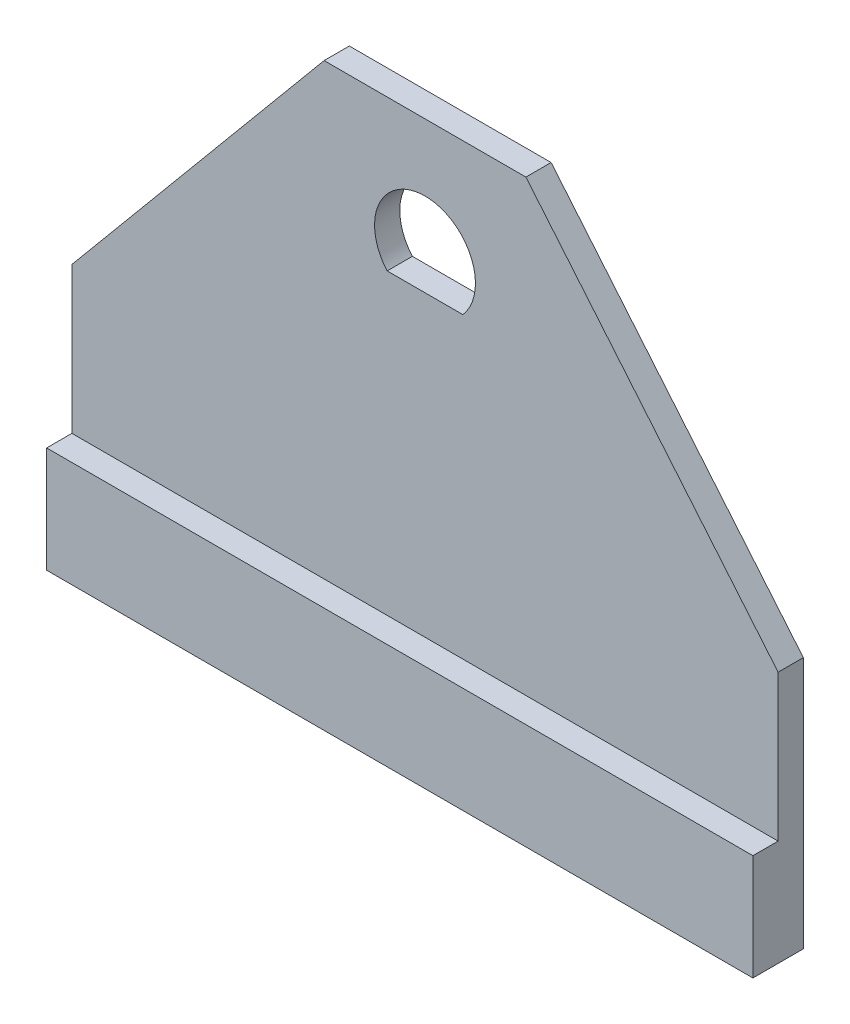
SolidWorks part; units mm, degrees
ref_plane "Front Plane" through (0, 0, 0) normal (0, 0, 1) x (1, 0, 0)
ref_plane "Top Plane" through (0, 0, 0) normal (0, 1, 0) x (1, 0, 0)
ref_plane "Right Plane" through (0, 0, 0) normal (1, 0, 0) x (0, 0, -1)
sketch "Sketch1" plane through (0, 0, 0) normal (0, 0, 1) x (1, 0, 0)
  line L0 (-149.5647, -59.3966) -> (-9.5647, -59.3966)
  line L1 (-9.5647, -59.3966) -> (-9.5647, -9.3966)
  line L2 (-9.5647, -9.3966) -> (-59.5647, 50.6034)
  line L3 (-59.5647, 50.6034) -> (-99.5647, 50.6034)
  line L4 (-99.5647, 50.6034) -> (-149.5647, -9.3966)
  line L5 (-149.5647, -9.3966) -> (-149.5647, -59.3966)
  line L6 (-99.5647, 50.6034) -> (-87.0647, 20.7435) construction
  line L7 (-72.0647, 20.7435) -> (-59.5647, 50.6034) construction
  line L8 (-149.5647, -38.3958) -> (-9.5647, -38.3958)
  line L10 (-87.0647, 20.7435) -> (-72.0647, 20.7435)
  arc A1 (-87.0647, 20.7435) -> (-72.0647, 20.7435) centre (-79.5647, 27.3579) cw
  dimension "D1" = 140
  dimension "D2" = 50
  dimension "D3" = 40
  dimension "D4" = 60
extrude "Boss-Extrude1" add sketch "Sketch1" along normal blind 5 from offset 10 contours L5 L8 L1 L2 L3 L4 L10 A1 region at (-79.5647, -2.5782, 0) offset against normal yes
extrude "Boss-Extrude2" add sketch "Sketch1<3>" against normal blind 10 contours L8 L5 L0 L1 region at (-79.5647, -48.8962, 0)
sketch "Sketch1<3>" plane through (0, 0, 0) normal (0, 0, 1) x (1, 0, 0) same geometry as "Sketch1"
